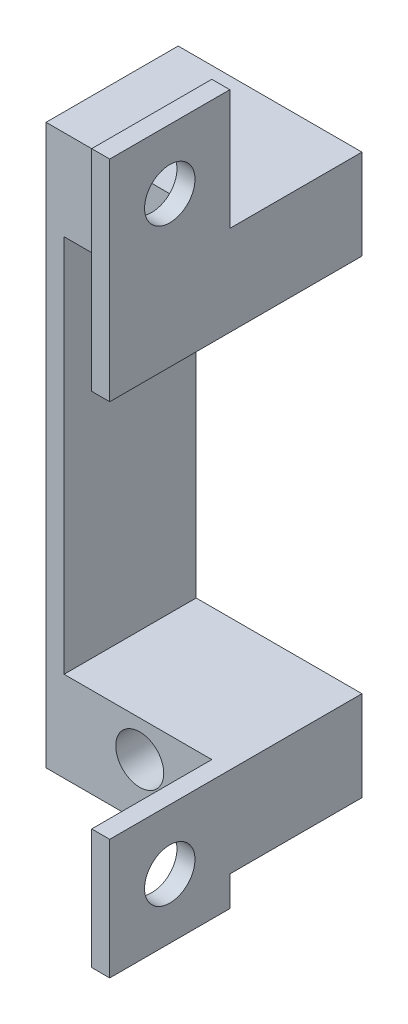
SolidWorks part; units mm, degrees
ref_plane "Front Plane" through (0, 0, 0) normal (0, 0, 1) x (1, 0, 0)
ref_plane "Top Plane" through (0, 0, 0) normal (0, 1, 0) x (1, 0, 0)
ref_plane "Right Plane" through (0, 0, 0) normal (1, 0, 0) x (0, 0, -1)
sketch "Sketch17" plane through (0, 0, 0) normal (0, 0, 1) x (1, 0, 0)
  line L1 (-9.5785, 42.9232) -> (-24.8785, 42.9232)
  line L2 (-9.5785, 42.9232) -> (-9.5785, 35.4232)
  line L3 (-9.5785, 35.4232) -> (-24.8785, 35.4232)
  line L4 (-24.8785, 42.9232) -> (-24.8785, 35.4232)
  dimension "D1" = 15.3
  dimension "D2" = 7.5
extrude "Boss-Extrude12" add sketch "Sketch17" along normal blind 11 separate body
sketch "Sketch18" plane through (0, 35.4232, 0) normal (0, -1, 0) x (1, 0, 0)
  line L0 (-24.8785, 0) -> (-9.5785, 0) construction
  line L1 (-24.8785, 11) -> (-23.3785, 11)
  line L2 (-24.8785, 11) -> (-24.8785, 0)
  line L3 (-24.8785, 0) -> (-23.3785, 0)
  line L4 (-23.3785, 11) -> (-23.3785, 0)
  dimension "D1" = 1.5
extrude "Boss-Extrude13" add sketch "Sketch18" along normal blind 15.775
sketch "Sketch19" plane through (0, 0, 11) normal (0, 0, 1) x (1, 0, 0)
  line L0 (-9.5785, 35.4232) -> (-9.5785, 42.9232) construction
  line L1 (-23.3785, 35.4232) -> (-9.5785, 35.4232) construction
  circle A0 centre (-17.0785, 38.4232) radius 2
  dimension "D1" = 7.5
  dimension "D2" = 3
  dimension "D3" = 4
extrude "Cut-Extrude2" cut sketch "Sketch19" against normal through all
sketch "Sketch21" plane through (0, 0, 11) normal (0, 0, 1) x (1, 0, 0)
  line L1 (-9.5785, 35.4232) -> (-11.0785, 35.4232)
  line L2 (-9.5785, 35.4232) -> (-9.5785, 42.9232)
  line L3 (-9.5785, 42.9232) -> (-11.0785, 42.9232)
  line L4 (-11.0785, 35.4232) -> (-11.0785, 42.9232)
  dimension "D1" = 1.5
  dimension "D2" = 7.5
extrude "Boss-Extrude14" add sketch "Sketch21" along normal blind 10 contours L2 L1 L4 L3
sketch "Sketch22" plane through (0, 42.9232, 0) normal (0, 1, 0) x (1, 0, 0)
  line L0 (-9.5785, -21) -> (-9.5785, 0) construction
  line L1 (-11.0785, -21) -> (-9.5785, -21)
  line L2 (-11.0785, -21) -> (-11.0785, -11)
  line L3 (-11.0785, -11) -> (-9.5785, -11)
  line L4 (-9.5785, -21) -> (-9.5785, -11)
extrude "Boss-Extrude15" add sketch "Sketch22" along normal blind 10
sketch "Sketch23" plane through (-11.0785, 0, 0) normal (-1, 0, 0) x (0, 0, 1)
  line L0 (21, 35.4232) -> (21, 52.9232) construction
  line L1 (11, 52.9232) -> (21, 52.9232) construction
  circle A0 centre (16, 47.9232) radius 2.1
  dimension "D1" = 4.2
  dimension "D2" = 5
  dimension "D3" = 5
extrude "Cut-Extrude4" cut sketch "Sketch23" against normal blind 10
ref_plane "Plane1" through (0, 19.6482, 0) normal (0, -1, 0) x (-1, 0, 0)
sketch "Sketch25" plane through (0, 19.6482, 0) normal (0, -1, 0) x (1, 0, 0)
  line L1 (-24.8785, 11) -> (-23.3785, 11)
  line L2 (-24.8785, 11) -> (-24.8785, 0)
  line L3 (-24.8785, 0) -> (-23.3785, 0)
  line L4 (-23.3785, 11) -> (-23.3785, 0)
extrude "Boss-Extrude16" add sketch "Sketch25" along normal blind 23.275
sketch "Sketch26" plane through (-23.3785, 0, 0) normal (1, 0, 0) x (0, 0, -1)
  line L0 (0, -3.6268) -> (0, 35.4232) construction
  line L1 (-11, -3.6268) -> (0, -3.6268)
  line L2 (-11, -3.6268) -> (-11, 3.8732)
  line L3 (-11, 3.8732) -> (0, 3.8732)
  line L4 (0, -3.6268) -> (0, 3.8732)
  dimension "D1" = 7.5
extrude "Boss-Extrude17" add sketch "Sketch26" along normal up to surface (13.8 mm away) up to face at (-9.5785, 45.8232, 16)
mirror "Mirror12" about plane through (0, 19.6482, 0) normal (0, -1, 0) of "Cut-Extrude2"
sketch "Sketch27" plane through (0, 0, 11) normal (0, 0, 1) x (1, 0, 0)
  line L0 (-9.5785, 3.8732) -> (-23.3785, 3.8732) construction
  line L1 (-9.5785, -3.6268) -> (-11.0785, -3.6268)
  line L2 (-9.5785, -3.6268) -> (-9.5785, 3.8732)
  line L3 (-9.5785, 3.8732) -> (-11.0785, 3.8732)
  line L4 (-11.0785, -3.6268) -> (-11.0785, 3.8732)
  dimension "D1" = 1.5
extrude "Boss-Extrude18" add sketch "Sketch27" along normal up to surface (10 mm away) up to face at (-10.3285, 44.1732, 21)
sketch "Sketch28" plane through (0, -3.6268, 0) normal (0, -1, 0) x (1, 0, 0)
  line L1 (-11.0785, 21) -> (-9.5785, 21)
  line L2 (-11.0785, 21) -> (-11.0785, 11)
  line L3 (-11.0785, 11) -> (-9.5785, 11)
  line L4 (-9.5785, 21) -> (-9.5785, 11)
extrude "Boss-Extrude19" add sketch "Sketch28" along normal blind 2.5
sketch "Sketch29" plane through (-11.0785, 0, 0) normal (-1, 0, 0) x (0, 0, 1)
  line L0 (21, -6.1268) -> (21, 3.8732) construction
  line L2 (21, 3.8732) -> (11, 3.8732) construction
  circle A0 centre (16, -1.1268) radius 2.1
  dimension "D1" = 4.2
  dimension "D2" = 5
  dimension "D3" = 5
extrude "Cut-Extrude5" cut sketch "Sketch29" against normal through all
